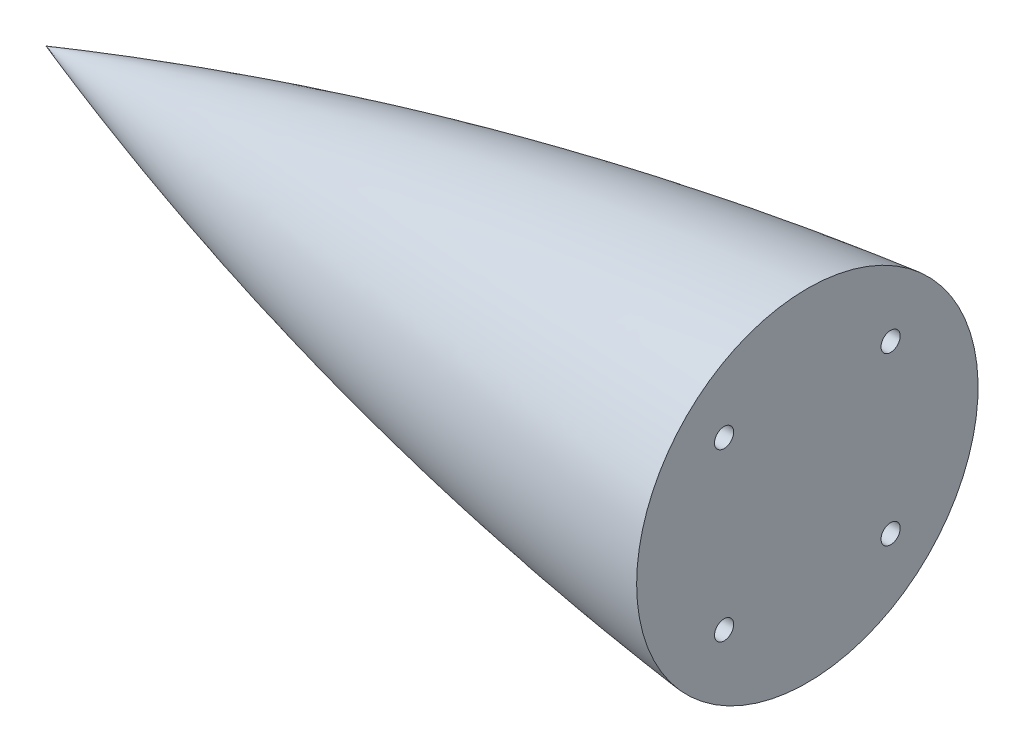
SolidWorks part; units mm, degrees
ref_plane "Front Plane" through (0, 0, 0) normal (0, 0, 1) x (1, 0, 0)
ref_plane "Top Plane" through (0, 0, 0) normal (0, 1, 0) x (1, 0, 0)
ref_plane "Right Plane" through (0, 0, 0) normal (1, 0, 0) x (0, 0, -1)
sketch "Sketch1" plane through (0, 0, 0) normal (0, 0, 1) x (1, 0, 0)
  line L0 (0, 0) -> (203.2, 0)
  line L1 (203.2, 0) -> (203.2, 45.5653)
  spline S0 degree 7 poles (-19.6355, -7.021) (15.101, 5.8385) (49.8375, 16.8716) (84.574, 26.1908) (119.3105, 33.8732) (154.047, 39.9741) (188.7835, 44.5305) (223.52, 47.5633) knots 0 0 0 0 0 0 0 0 1 1 1 1 1 1 1 1 construction
  spline S1 degree 7 poles (0, 0) (29.0286, 10.0158) (58.0571, 18.7863) (87.0857, 26.3707) (116.1143, 32.8126) (145.1429, 38.1447) (174.1714, 42.3905) (203.2, 45.5653) knots 0.080753 0.080753 0.080753 0.080753 0.080753 0.080753 0.080753 0.080753 0.916432 0.916432 0.916432 0.916432 0.916432 0.916432 0.916432 0.916432
  dimension "D1" = 203.2
revolve "Revolve1" add sketch "Sketch1" angle 360 about L0
hole_wizard "1/4-20 Tapped Hole1" positions "Sketch5" profile "Sketch4" tap size "1/4-20" standard "ANSI Inch"
sketch "Sketch5" plane through (203.2, 0, 0) normal (1, 0, 0) x (0, 0, -1)
  line L4 (0, 0) -> (0, 26.4434) construction
  line L6 (0, 0) -> (-33.7923, 0) construction
  circle A0 centre (0, 0) radius 45.5653 construction
  point P0 (-22.225, 22.225)
  point P31 (0, 30.3377)
  point P32 (-19.3458, 28.2021)
  point P33 (0, 0)
  point P34 (22.225, 22.225)
  point P35 (0, 0)
  point P36 (22.225, -22.225)
  point P37 (-22.225, -22.225)
  dimension "D1" = 44.45
  dimension "D2" = 44.45
sketch "Sketch4" plane through (203.2, 22.225, 22.225) normal (0, 1, 0) x (0, 0, -1)
  line L0 (0, 0) -> (0, 52.3338)
  line L1 (0, 52.3338) -> (2.5527, 50.8)
  line L2 (2.5527, 50.8) -> (2.5527, 0)
  line L5 (2.5527, 0) -> (0, 0)
  line L10 (0, 52.3338) -> (-2.5527, 50.8) construction
  line L11 (0, -6.35) -> (0, 107.95) construction
  dimension "Tap Drill Dia." = 5.1054
  dimension "Tap Drill Depth" = 50.8
  dimension "Drill Angle" = 118
